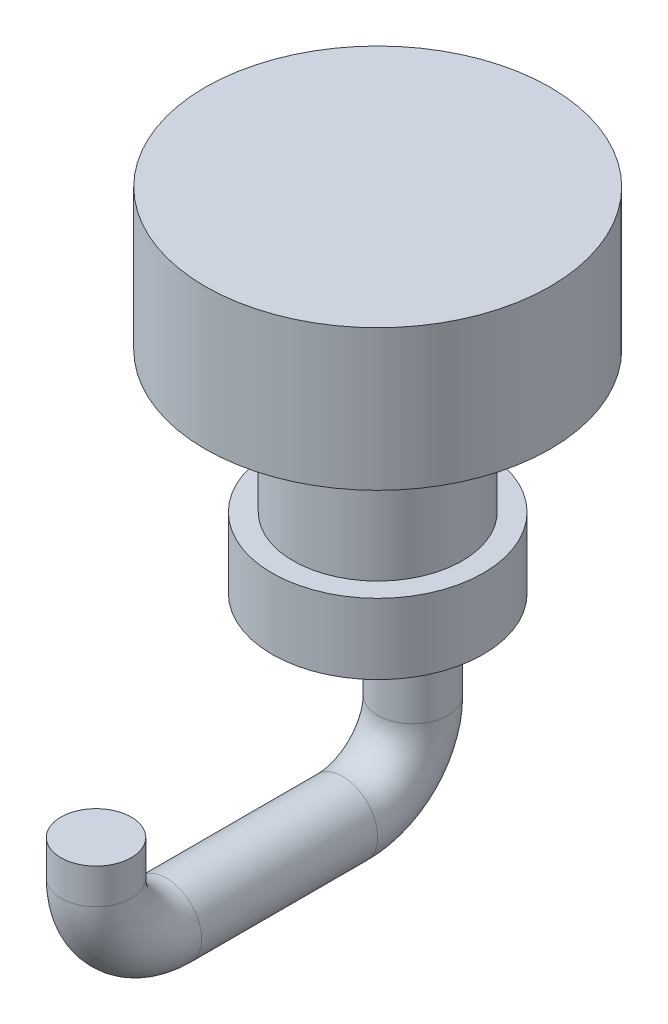
SolidWorks part; units mm, degrees
ref_plane "Front Plane" through (0, 0, 0) normal (0, 0, 1) x (1, 0, 0)
ref_plane "Top Plane" through (0, 0, 0) normal (0, 1, 0) x (1, 0, 0)
ref_plane "Right Plane" through (0, 0, 0) normal (1, 0, 0) x (0, 0, -1)
sketch "Sketch1" plane through (0, 0, 0) normal (0, 0, 1) x (1, 0, 0)
  line L0 (0, 0) -> (6.223, 0)
  line L1 (6.223, 0) -> (6.223, -5.08)
  line L2 (6.223, -5.08) -> (3.048, -5.08)
  line L3 (3.048, -5.08) -> (3.048, -10.16)
  line L4 (3.048, -10.16) -> (3.81, -10.16)
  line L5 (3.81, -10.16) -> (3.81, -12.7)
  line L6 (3.81, -12.7) -> (0, -12.7)
  line L7 (0, -12.7) -> (0, 0)
  dimension "D1" = 12.7
  dimension "D2" = 2.54
  dimension "D3" = 5.08
  dimension "D4" = 6.223
  dimension "D5" = 3.048
  dimension "D6" = 3.81
revolve "button body" add sketch "Sketch1" angle 360 about L7
ref_plane "spring path" through (4.318, 0, 0) normal (1, 0, 0) x (0, 0, -1)
sketch "Sketch2" plane through (4.318, 0, 0) normal (1, 0, 0) x (0, 0, -1)
  spline S0 degree 3 poles (2.9542, -4.563) (1.8538, -5.2739) (-1.4839, -5.7786) (3.0242, -6.9827) knots 0 0 0 0 1 1 1 1
ref_plane "spring cross section" through (0, 0, -3.0242) normal (0, 0, 1) x (1, 0, 0)
ref_axis "center axis" through (0, 0, 0) along (0, -1, 0)
pattern_circular "moar springs" count 4 over 360 about axis through (0, 0, 0) along (0, -1, 0) of bodies 101 102
ref_plane "spring cutoff" through (0, -6.858, 0) normal (0, 1, 0) x (1, 0, 0)
sketch "Sketch5" plane through (0, -6.858, 0) normal (0, 1, 0) x (1, 0, 0)
  line L1 (-5.4573, -1.4157) -> (-3.0941, -1.4157)
  line L2 (-5.4573, -1.4157) -> (-5.4573, -3.506)
  line L3 (-5.4573, -3.506) -> (-3.0941, -3.506)
  line L4 (-3.0941, -1.4157) -> (-3.0941, -3.506)
  line L5 (1.4555, -3.3381) -> (3.3946, -3.3381)
  line L6 (1.4555, -3.3381) -> (1.4555, -5.4537)
  line L7 (1.4555, -5.4537) -> (3.3946, -5.4537)
  line L8 (3.3946, -3.3381) -> (3.3946, -5.4537)
  line L9 (3.3946, 3.1587) -> (5.2632, 3.1587)
  line L10 (3.3946, 3.1587) -> (3.3946, 1.2698)
  line L11 (3.3946, 1.2698) -> (5.2632, 1.2698)
  line L12 (5.2632, 3.1587) -> (5.2632, 1.2698)
  line L13 (-3.4934, 5.5558) -> (-1.1945, 5.5558)
  line L14 (-3.4934, 5.5558) -> (-3.4934, 3.1587)
  line L15 (-3.4934, 3.1587) -> (-1.1945, 3.1587)
  line L16 (-1.1945, 5.5558) -> (-1.1945, 3.1587)
ref_plane "curve hook" through (0, 0, 0) normal (0, 0, 1) x (1, 0, 0)
ref_point "curve start"
ref_plane "hook plane" through (0, 0, 0) normal (1, 0, 0) x (0, 0, -1)
sketch "Sketch12" plane through (0, 0, 0) normal (1, 0, 0) x (0, 0, -1)
  line L0 (0, -12.7) -> (0, -16.51)
  line L1 (-1.27, -17.78) -> (-7.62, -17.78)
  line L2 (-8.89, -16.51) -> (-8.89, -15.24)
  arc A0 (0, -16.51) -> (-1.27, -17.78) centre (-1.27, -16.51) cw
  arc A1 (-7.62, -17.78) -> (-8.89, -16.51) centre (-7.62, -16.51) cw
  point P8 (0, -17.78)
  point P11 (-8.89, -17.78)
  dimension "D2" = 1.27
  dimension "D4" = 1.27
  dimension "D1" = 5.08
  dimension "D3" = 2.54
  dimension "D5" = 6.35
sketch "Sketch13" plane through (0, -12.7, 0) normal (0, -1, 0) x (-1, 0, 0)
  circle A0 centre (0, 1.27) radius 1.27
sweep "hook for baton" add profiles "Sketch13" path "Sketch12"
